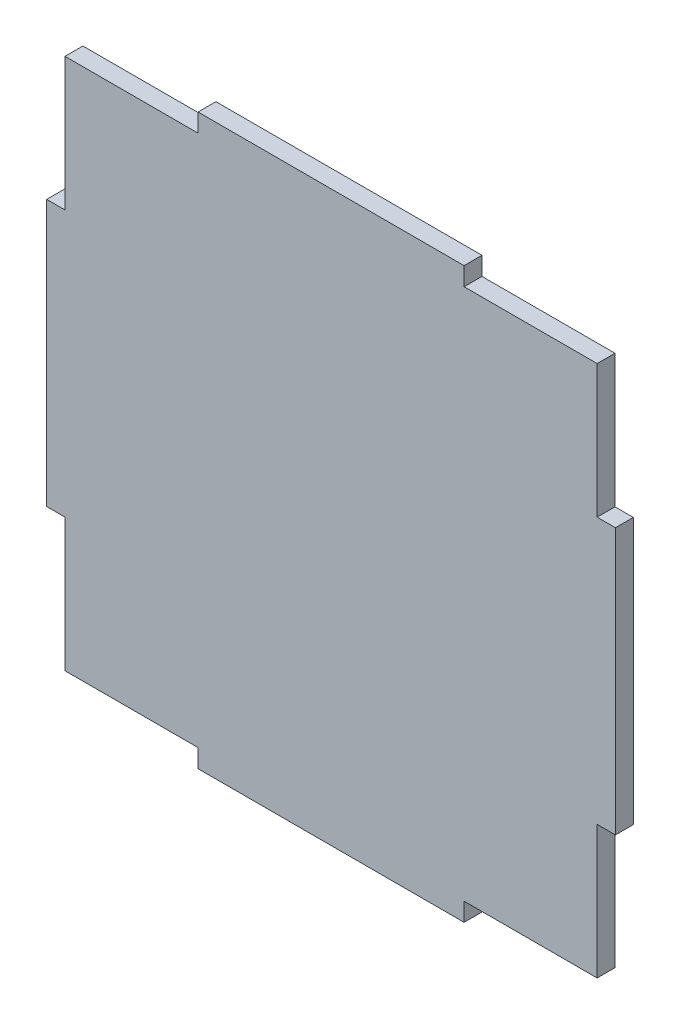
SolidWorks part; units mm, degrees
ref_plane "Front Plane" through (0, 0, 0) normal (0, 0, 1) x (1, 0, 0)
ref_plane "Top Plane" through (0, 0, 0) normal (0, 1, 0) x (1, 0, 0)
ref_plane "Right Plane" through (0, 0, 0) normal (1, 0, 0) x (0, 0, -1)
sketch "Sketch1" plane through (0, 0, 0) normal (0, 0, 1) x (1, 0, 0)
  line L1 (-50, 50) -> (50, 50)
  line L2 (-50, 50) -> (-50, -50)
  line L3 (-50, -50) -> (50, -50)
  line L4 (50, 50) -> (50, -50)
  line L5 (-50, 50) -> (50, -50) construction
  line L6 (-50, -50) -> (50, 50) construction
  point P0 (0, 0)
  dimension "D1" = 100
  dimension "D2" = 100
extrude "Boss-Extrude1" add sketch "Sketch1" along normal blind 3.36
sketch "Sketch2" [suppressed] plane through (0, 0, 3.36) normal (0, 0, 1) x (1, 0, 0)
  line L0 (50, 50) -> (-50, 50) construction
  line L1 (-25, 50) -> (25, 50)
  line L2 (-25, 50) -> (-25, 53.36)
  line L3 (-25, 53.36) -> (25, 53.36)
  line L4 (25, 50) -> (25, 53.36)
  line L5 (0, 0) -> (0, 53.36) construction
  line L6 (0, 0) -> (50, 0) construction
  line L7 (50, -50) -> (50, 50) construction
  dimension "D1" = 3.36
  dimension "D2" = 50
sketch "Sketch8" plane through (0, 0, 0) normal (0, 0, -1) x (-1, 0, 0)
  line L0 (0, 0) -> (0, 50) construction
  line L1 (-50, 50) -> (50, 50) construction
  line L2 (0, 0) -> (50, 0) construction
  line L3 (50, 50) -> (50, -50) construction
  line L5 (-25, 50) -> (25, 50)
  line L6 (-25, 50) -> (-25, 53.44)
  line L7 (-25, 53.44) -> (25, 53.44)
  line L8 (25, 50) -> (25, 53.44)
  dimension "D1" = 50
  dimension "D2" = 3.44
extrude "Boss-Extrude4" add sketch "Sketch8" against normal blind 3.36
mirror "Mirror4" about plane through (0, 0, 0) normal (0, 1, 0) of "Boss-Extrude4"
sketch "Sketch9" plane through (0, 0, 0) normal (0, 0, -1) x (-1, 0, 0)
  line L0 (0, 0) -> (50, 0) construction
  line L1 (50, 50) -> (50, -50) construction
  line L3 (50, 25) -> (53.44, 25)
  line L4 (50, 25) -> (50, -25)
  line L5 (50, -25) -> (53.44, -25)
  line L6 (53.44, 25) -> (53.44, -25)
  dimension "D1" = 50
  dimension "D2" = 3.44
extrude "Boss-Extrude5" add sketch "Sketch9" against normal blind 3.36
mirror "Mirror5" about plane through (0, 0, 0) normal (1, 0, 0) of "Boss-Extrude5"
sketch "Sketch10" plane through (0, 0, 3.36) normal (0, 0, 1) x (1, 0, 0)
  line L0 (0, 0) -> (0, 50) construction
  line L1 (50, 50) -> (25, 50) construction
  line L3 (-22.1665, 50) -> (22.1665, 50)
  line L4 (-22.1665, 50) -> (-22.1665, 40.4825)
  line L5 (-22.1665, 40.4825) -> (22.1665, 40.4825)
  line L6 (22.1665, 50) -> (22.1665, 40.4825)
  dimension "D1" = 9.5175
  dimension "D2" = 44.3329
extrude "Cut-Extrude1" [suppressed] cut sketch "Sketch10" against normal blind 3.36
mirror "Mirror6" [suppressed] about plane through (0, 0, 0) normal (0, 1, 0)
sketch "Sketch11" plane through (0, 0, 3.36) normal (0, 0, 1) x (1, 0, 0)
  line L0 (0, 0) -> (50, 0) construction
  line L1 (50, -50) -> (50, -25) construction
  line L3 (50, 18.3322) -> (46.2005, 18.3322)
  line L4 (50, 18.3322) -> (50, -18.3322)
  line L5 (50, -18.3322) -> (46.2005, -18.3322)
  line L6 (46.2005, 18.3322) -> (46.2005, -18.3322)
  point P9 (50, 0)
  dimension "D1" = 3.7995
  dimension "D2" = 36.6643
extrude "Cut-Extrude2" [suppressed] cut sketch "Sketch11" against normal through all
equation "\"Sheet Thickness\"= 3.36mm"
equation "\"Height\"= 100mm"
equation "\"Length\"= 100mm"
equation "\"Width\"= 100mm"
equation "\"D1@Boss-Extrude1\"=\"Sheet Thickness\""
equation "\"D1@Sketch2\"=\"Sheet Thickness\""
equation "\"D2@Sketch2\"=\"Height\"/2"
equation "\"Kerf\"= .08mm"
equation "\"D2@Sketch9\"=\"Sheet Thickness\"+\"Kerf\""
equation "\"D1@Sketch9\"   = \"Length\"/2"
equation "\"D1@Sketch8\"     = \"Width\"/2"
equation "\"D2@Sketch8\"=\"Sheet Thickness\"+\"Kerf\""
equation "\"D1@Sketch10\"=\"Sheet Thickness\"-\"Kerf\""
equation "\"D2@Sketch10\" = \"Width\"/2"
equation "\"D1@Sketch11\"=\"Sheet Thickness\"-\"Kerf\""
equation "\"D2@Sketch11\"=\"Height\"/2"
